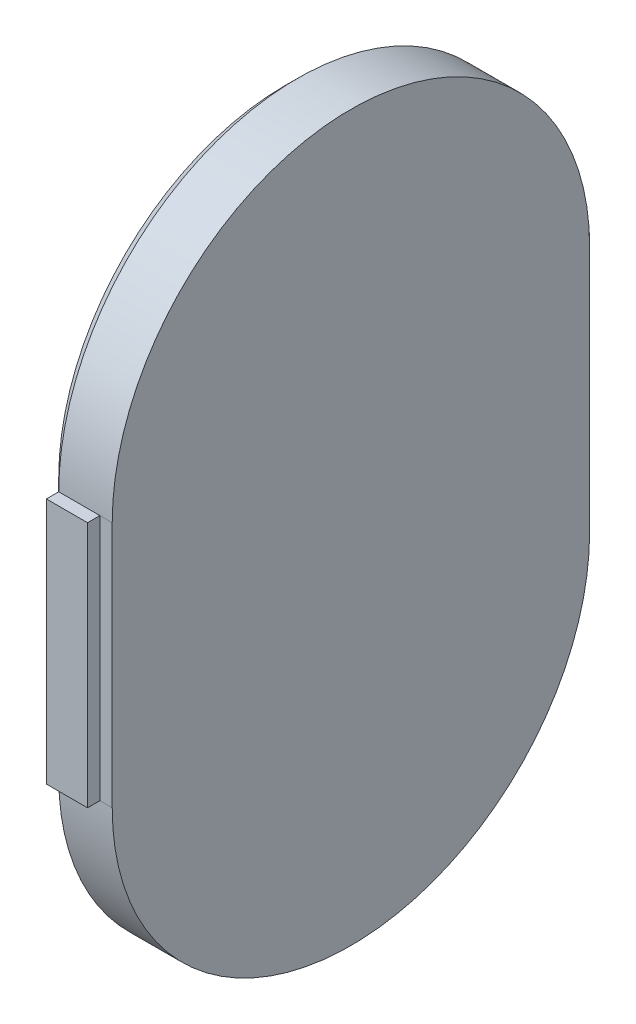
SolidWorks part; units mm, degrees
ref_plane "Front Plane" through (0, 0, 0) normal (0, 0, 1) x (1, 0, 0)
ref_plane "Top Plane" through (0, 0, 0) normal (0, 1, 0) x (1, 0, 0)
ref_plane "Right Plane" through (0, 0, 0) normal (1, 0, 0) x (0, 0, -1)
sketch "Sketch1" plane through (0, 0, 0) normal (1, 0, 0) x (0, 0, -1)
  line L0 (-73.2, 110) -> (-73.2, 116)
  line L1 (-61.6, 116) -> (-61.6, 110)
  arc A0 (-61.6, 110) -> (-67.4, 104.2) centre (-67.4, 110) cw
  arc A1 (-67.4, 104.2) -> (-73.2, 110) centre (-67.4, 110) cw
  arc A2 (-73.2, 116) -> (-67.4, 121.8) centre (-67.4, 116) cw
  arc A3 (-67.4, 121.8) -> (-61.6, 116) centre (-67.4, 116) cw
extrude "Boss-Extrude1" add sketch "Sketch1" along normal blind 1.6 from offset 63 offset against normal yes
chamfer "Chamfer1" distance 0.3 angle 45 4 edges at (-63, 104.2, 67.4) (-63, 113, 61.6) (-63, 113, 73.2) (-63, 121.8, 67.4)
sketch "Sketch2" plane through (0, 0, 0) normal (0, 0, 1) x (1, 0, 0)
  line L1 (-62.7, 110) -> (-61.7, 110)
  line L2 (-62.7, 110) -> (-62.7, 116)
  line L3 (-62.7, 116) -> (-61.7, 116)
  line L4 (-61.7, 110) -> (-61.7, 116)
extrude "Boss-Extrude2" add sketch "Sketch2" along normal blind 0.31 from offset 61.3
sketch "Sketch3" plane through (0, 0, 0) normal (0, 0, 1) x (1, 0, 0)
  line L1 (-62.7, 110) -> (-61.7, 110)
  line L2 (-62.7, 110) -> (-62.7, 116)
  line L3 (-62.7, 116) -> (-61.7, 116)
  line L4 (-61.7, 110) -> (-61.7, 116)
extrude "Boss-Extrude3" add sketch "Sketch3" along normal blind 0.31 from offset 73.19
sketch "Sketch4" plane through (0, 0, 0) normal (0, 0, 1) x (1, 0, 0)
  line L1 (-63.1, 104.1) -> (-62.4, 104.1)
  line L2 (-63.1, 104.1) -> (-63.1, 105.4)
  line L3 (-63.1, 105.4) -> (-62.4, 105.4)
  line L4 (-62.4, 104.1) -> (-62.4, 105.4)
extrude "Boss-Extrude4" add sketch "Sketch4" along normal blind 3 from offset 65.9 separate body
combine bodies "Combine1" operation type subtract main body 103 bodies to subtract 104
